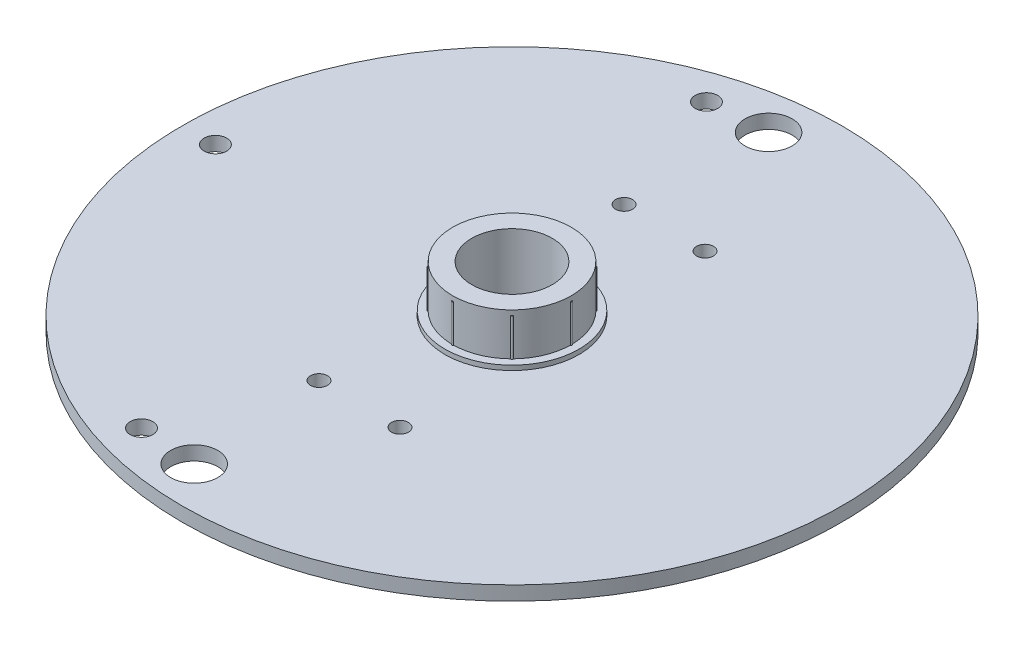
SolidWorks part; units mm, degrees
ref_plane "Front Plane" through (0, 0, 0) normal (0, 0, 1) x (1, 0, 0)
ref_plane "Top Plane" through (0, 0, 0) normal (0, 1, 0) x (1, 0, 0)
ref_plane "Right Plane" through (0, 0, 0) normal (1, 0, 0) x (0, 0, -1)
sketch "Sketch1" plane through (0, 0, 0) normal (0, 1, 0) x (1, 0, 0)
  circle A0 centre (0, 0) radius 70
  dimension "D1" = 140
extrude "base-plate" add sketch "Sketch1" along normal blind 3
sketch "Sketch2" plane through (0, 3, 0) normal (0, 1, 0) x (1, 0, 0)
  circle A0 centre (0, 0) radius 14.25
  dimension "D1" = 28.5
extrude "bearing-stepup" add sketch "Sketch2" along normal blind 1
sketch "Sketch3" plane through (0, 4, 0) normal (0, 1, 0) x (1, 0, 0)
  circle A0 centre (0, 0) radius 12.6
  dimension "D1" = 25.2
extrude "bearing-sitting" add sketch "Sketch3" along normal blind 9
sketch "Sketch4" plane through (0, 4, 0) normal (0, 1, 0) x (1, 0, 0)
  circle A0 centre (0, 12.6) radius 0.2
  circle A1 centre (0, 0) radius 12.6 construction
  circle A2 centre (0, 0) radius 12.6 construction
  circle A3 centre (8.9095, 8.9095) radius 0.2
  circle A4 centre (12.6, 0) radius 0.2
  circle A5 centre (8.9095, -8.9095) radius 0.2
  circle A6 centre (0, -12.6) radius 0.2
  circle A7 centre (-8.9095, -8.9095) radius 0.2
  circle A8 centre (-12.6, 0) radius 0.2
  circle A9 centre (-8.9095, 8.9095) radius 0.2
  point P23 (0, 0)
  dimension "D1" = 0.4
  dimension "D2" = 8
extrude "bearing-sitting-grid" add sketch "Sketch4" along normal blind 8
sketch "Sketch5" plane through (0, 0, 0) normal (0, -1, 0) x (1, 0, 0)
  line L2 (7.15, 0) -> (-7.15, 0) construction
  circle A0 centre (-18.7, 60) radius 2.4
  circle A1 centre (-63, 0) radius 2.4
  circle A2 centre (-18.7, -60) radius 2.4
  dimension "D3" = 4.8
  dimension "D4" = 4.8
  dimension "D1" = 63
  dimension "D2" = 60
  dimension "D5" = 18.7
extrude "m4-screw-clearance-holes" cut sketch "Sketch5" against normal through all contours A0 | A1 | A2 region at (-18.7, 0, 60) region at (-63, 0, 0)
sketch "Sketch6" plane through (0, 0, 0) normal (0, -1, 0) x (1, 0, 0)
  line L0 (7.15, 0) -> (-7.15, 0) construction
  circle A0 centre (-6.5, 61) radius 5
  circle A1 centre (-6.5, -61) radius 5
  dimension "D3" = 10
  dimension "D1" = 61
  dimension "D2" = 6.5
extrude "holes-reserved-for-rods" cut sketch "Sketch6" against normal through all
sketch "Sketch8" plane through (0, 13, 0) normal (0, 1, 0) x (1, 0, 0)
  circle A0 centre (0, 0) radius 8.55
  dimension "D1" = 17.1
extrude "Cut-Extrude1" cut sketch "Sketch8" against normal through all
sketch "Sketch9" plane through (0, 3, 0) normal (0, 1, 0) x (1, 0, 0)
  line L0 (0, -7.15) -> (0, 7.15) construction
  line L1 (-7.15, 0) -> (7.15, 0) construction
  circle A0 centre (-8.6, 32.4) radius 1.8
  circle A1 centre (8.6, 32.4) radius 1.8
  circle A2 centre (8.6, -32.4) radius 1.8
  circle A3 centre (-8.6, -32.4) radius 1.8
  dimension "D1" = 3.6
  dimension "D2" = 8.6
  dimension "D3" = 32.4
extrude "Cut-Extrude2" cut sketch "Sketch9" against normal up to next
